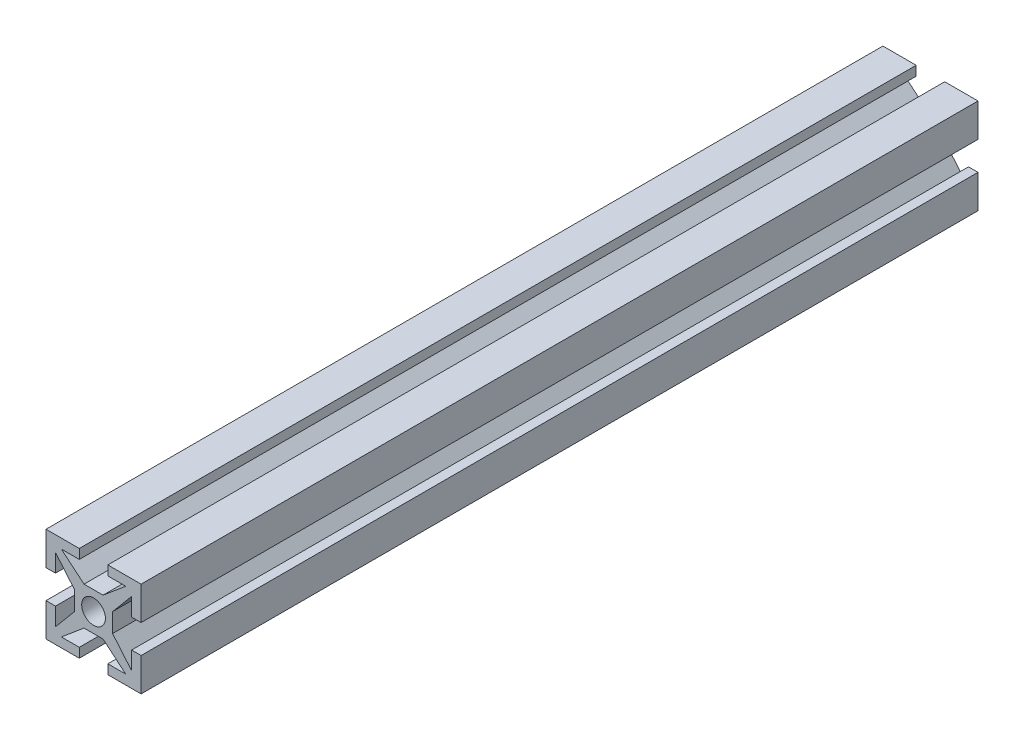
SolidWorks part; units mm, degrees
ref_plane "Front Plane" through (0, 0, 0) normal (0, 0, 1) x (1, 0, 0)
ref_plane "Top Plane" through (0, 0, 0) normal (0, 1, 0) x (1, 0, 0)
ref_plane "Right Plane" through (0, 0, 0) normal (1, 0, 0) x (0, 0, -1)
sketch "Esquisse2" plane through (0, 0, 0) normal (0, 0, 1) x (1, 0, 0)
  line L0 (-1, -2) -> (1, -2)
  line L1 (1, -2) -> (3.3835, -4)
  line L2 (3.3835, -4) -> (1.5, -4)
  line L3 (1.5, -4) -> (1.5, -5)
  line L4 (1.5, -5) -> (5, -5)
  line L5 (-1, -2) -> (-3.3835, -4)
  line L6 (-3.3835, -4) -> (-1.5, -4)
  line L7 (-1.5, -4) -> (-1.5, -5)
  line L8 (-1.5, -5) -> (-5, -5)
  line L9 (-5, -5) -> (-5, -1.5)
  line L10 (-5, -1.5) -> (-4, -1.5)
  line L11 (-4, -1.5) -> (-4, -3.3835)
  line L12 (-4, -3.3835) -> (-2, -1)
  line L13 (-2, -1) -> (-2, 1)
  line L14 (-2, 1) -> (-4, 3.3835)
  line L15 (-4, 3.3835) -> (-4, 1.5)
  line L16 (-4, 1.5) -> (-5, 1.5)
  line L17 (-5, 1.5) -> (-5, 5)
  line L18 (-5, 5) -> (-1.5, 5)
  line L19 (-1.5, 5) -> (-1.5, 4)
  line L20 (-1.5, 4) -> (-3.3835, 4)
  line L21 (-3.3835, 4) -> (-1, 2)
  line L22 (-1, 2) -> (1, 2)
  line L23 (1, 2) -> (3.3835, 4)
  line L24 (3.3835, 4) -> (1.5, 4)
  line L25 (1.5, 4) -> (1.5, 5)
  line L26 (1.5, 5) -> (5, 5)
  line L27 (5, 5) -> (5, 1.5)
  line L28 (5, 1.5) -> (4, 1.5)
  line L29 (4, 1.5) -> (4, 3.3835)
  line L30 (4, 3.3835) -> (2, 1)
  line L31 (2, -1) -> (2, 1)
  line L32 (2, -1) -> (4, -3.3835)
  line L33 (4, -3.3835) -> (4, -1.5)
  line L34 (4, -1.5) -> (5, -1.5)
  line L35 (5, -1.5) -> (5, -5)
  circle A0 centre (0, 0) radius 1.25
  point P4 (0, -2)
  point P34 (0, 2)
  point P40 (2, 0)
  dimension "D4" = 2.5
  dimension "D1" = 2
  dimension "D2" = 3.5
  dimension "D3" = 1
  dimension "D5" = 10
  dimension "D6" = 10
  dimension "D7" = 140
  dimension "D8" = 4
  dimension "D9" = 4
  dimension "D10" = 3.5
  dimension "D11" = 3
extrude "Boss.-Extru.1" add sketch "Esquisse2" along normal blind 88
